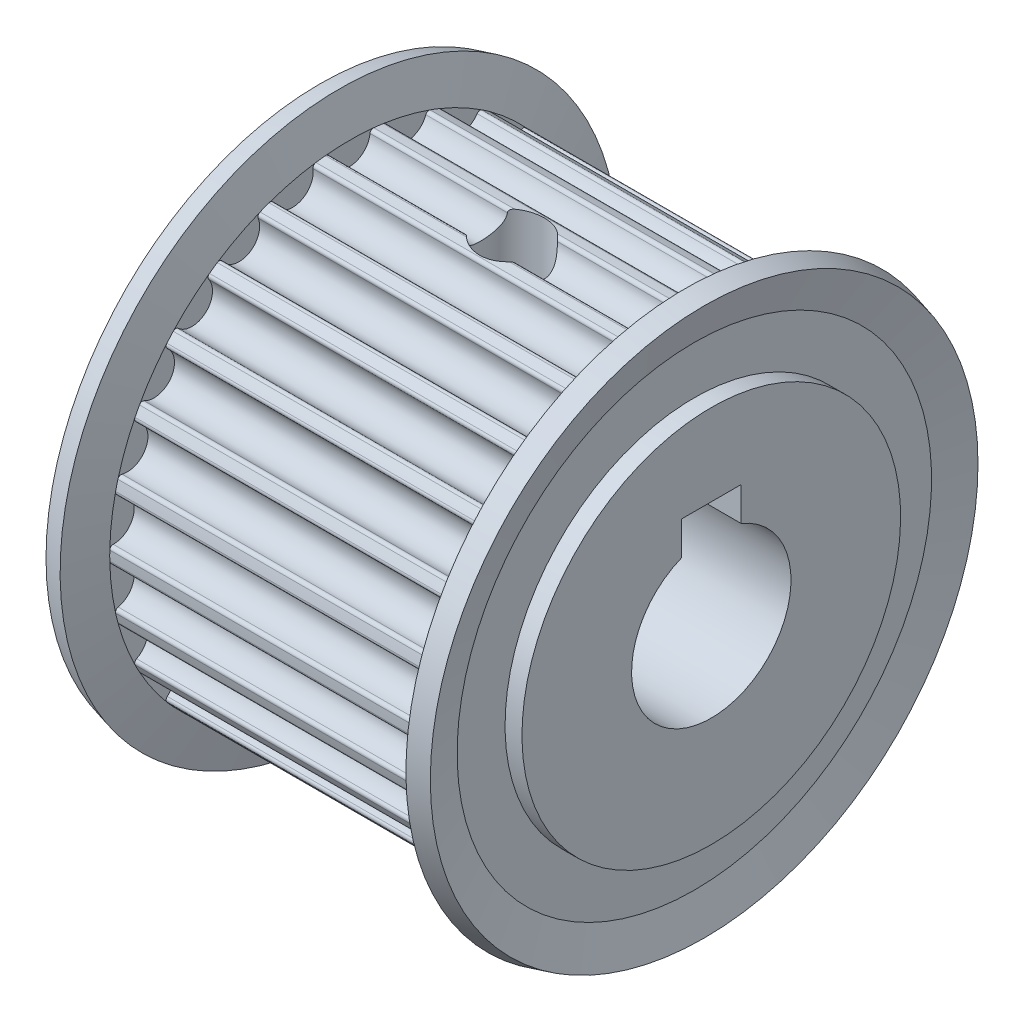
SolidWorks part; units mm, degrees
ref_plane "Front Plane" through (0, 0, 0) normal (0, 0, 1) x (1, 0, 0)
ref_plane "Top Plane" through (0, 0, 0) normal (0, 1, 0) x (1, 0, 0)
ref_plane "Right Plane" through (0, 0, 0) normal (1, 0, 0) x (0, 0, -1)
ref_plane "Plane1" through (0, 0, 0) normal (0, 0, 1) x (1, 0, 0)
sketch "Sketch1" plane through (0, 0, 0) normal (0, 0, 1) x (1, 0, 0)
  line L0 (0, 0) -> (0, 9.5)
  line L1 (0, 9.5) -> (0.85, 9.5)
  line L2 (0.85, 9.5) -> (0.85, 11.9033)
  line L3 (0.85, 11.9033) -> (0.3576, 13.7412)
  line L4 (0.3576, 13.7412) -> (1.3235, 14)
  line L5 (1.3235, 14) -> (1.85, 12.035)
  line L6 (1.85, 12.035) -> (18.15, 12.035)
  line L7 (18.15, 12.035) -> (18.6765, 14)
  line L8 (18.6765, 14) -> (19.6424, 13.7412)
  line L9 (19.6424, 13.7412) -> (19.15, 11.9033)
  line L10 (19.15, 11.9033) -> (19.15, 9.5)
  line L11 (19.15, 9.5) -> (20, 9.5)
  line L12 (20, 9.5) -> (20, 0)
  line L13 (20, 0) -> (0, 0)
  line L14 (20, 0) -> (0, 0) construction
revolve "Revolve1" add sketch "Sketch1" angle 360 about L14 reverse direction yes
ref_plane "Plane2" through (10, 0, 0) normal (1, 0, 0) x (0, 0, -1)
sketch "Sketch2" plane through (10, 0, 0) normal (1, 0, 0) x (0, 0, -1)
  line L0 (-1.2493, 12.352) -> (-1.2111, 11.9739)
  line L1 (1.2111, 11.9739) -> (1.2493, 12.352)
  arc A0 (-1.2111, 11.9739) -> (-1.0248, 11.8218) centre (-1.194, 11.8048) cw
  arc A1 (-1.0248, 11.8218) -> (1.0248, 11.8218) centre (0, 11.925) ccw
  arc A2 (1.0248, 11.8218) -> (1.2111, 11.9739) centre (1.194, 11.8048) cw
  arc A3 (1.2493, 12.352) -> (-1.2493, 12.352) centre (0, 0) ccw
extrude "Cut-Extrude1" cut sketch "Sketch2" against normal blind 8.15 and the other way blind 8.15
ref_plane "Plane3" through (10, 0, 0) normal (1, 0, 0) x (0, 0, -1)
sketch "Sketch3" plane through (10, 0, 0) normal (1, 0, 0) x (0, 0, -1)
  line L0 (-4.169, 11.6941) -> (-4.0414, 11.3361)
  line L1 (-1.6897, 11.9158) -> (-1.743, 12.292)
  arc A0 (-4.0414, 11.3361) -> (-3.8242, 11.233) centre (-3.9843, 11.176) cw
  arc A1 (-3.8242, 11.233) -> (-1.8341, 11.7235) centre (-2.8538, 11.5785) ccw
  arc A2 (-1.8341, 11.7235) -> (-1.6897, 11.9158) centre (-1.6658, 11.7475) cw
  arc A3 (-1.743, 12.292) -> (-4.169, 11.6941) centre (0, 0) ccw
extrude "Cut-Extrude2" cut sketch "Sketch3" against normal blind 8.15 and the other way blind 8.15
ref_plane "Plane4" through (10, 0, 0) normal (1, 0, 0) x (0, 0, -1)
sketch "Sketch4" plane through (10, 0, 0) normal (1, 0, 0) x (0, 0, -1)
  line L0 (-6.8465, 10.3566) -> (-6.6369, 10.0396)
  line L1 (-4.4922, 11.1652) -> (-4.634, 11.5177)
  arc A0 (-6.6369, 10.0396) -> (-6.4013, 9.9914) centre (-6.5432, 9.8977) cw
  arc A1 (-6.4013, 9.9914) -> (-4.5864, 10.9439) centre (-5.5418, 10.5591) ccw
  arc A2 (-4.5864, 10.9439) -> (-4.4922, 11.1652) centre (-4.4288, 11.0075) cw
  arc A3 (-4.634, 11.5177) -> (-6.8465, 10.3566) centre (0, 0) ccw
extrude "Cut-Extrude3" cut sketch "Sketch4" against normal blind 8.15 and the other way blind 8.15
ref_plane "Plane5" through (10, 0, 0) normal (1, 0, 0) x (0, 0, -1)
sketch "Sketch5" plane through (10, 0, 0) normal (1, 0, 0) x (0, 0, -1)
  line L0 (-9.126, 8.4171) -> (-8.8467, 8.1595)
  line L1 (-7.0337, 9.7657) -> (-7.2558, 10.074)
  arc A0 (-8.8467, 8.1595) -> (-8.6064, 8.1692) centre (-8.7217, 8.0443) cw
  arc A1 (-8.6064, 8.1692) -> (-7.0722, 9.5283) centre (-7.9077, 8.926) ccw
  arc A2 (-7.0722, 9.5283) -> (-7.0337, 9.7657) centre (-6.9343, 9.6277) cw
  arc A3 (-7.2558, 10.074) -> (-9.126, 8.4171) centre (0, 0) ccw
extrude "Cut-Extrude4" cut sketch "Sketch5" against normal blind 8.15 and the other way blind 8.15
ref_plane "Plane6" through (10, 0, 0) normal (1, 0, 0) x (0, 0, -1)
sketch "Sketch6" plane through (10, 0, 0) normal (1, 0, 0) x (0, 0, -1)
  line L0 (-10.8752, 5.9886) -> (-10.5423, 5.8053)
  line L1 (-9.1664, 7.7986) -> (-9.4558, 8.0449)
  arc A0 (-10.5423, 5.8053) -> (-10.3113, 5.8721) centre (-10.3934, 5.7233) cw
  arc A1 (-10.3113, 5.8721) -> (-9.147, 7.559) centre (-9.8141, 6.7742) ccw
  arc A2 (-9.147, 7.559) -> (-9.1664, 7.7986) centre (-9.0369, 7.6885) cw
  arc A3 (-9.4558, 8.0449) -> (-10.8752, 5.9886) centre (0, 0) ccw
extrude "Cut-Extrude5" cut sketch "Sketch6" against normal blind 8.15 and the other way blind 8.15
ref_plane "Plane7" through (10, 0, 0) normal (1, 0, 0) x (0, 0, -1)
sketch "Sketch7" plane through (10, 0, 0) normal (1, 0, 0) x (0, 0, -1)
  line L0 (-11.9923, 3.2119) -> (-11.6253, 3.1136)
  line L1 (-10.7663, 5.3784) -> (-11.1063, 5.5482)
  arc A0 (-11.6253, 3.1136) -> (-11.417, 3.2338) centre (-11.461, 3.0697) cw
  arc A1 (-11.417, 3.2338) -> (-10.6902, 5.1503) centre (-11.1501, 4.2287) ccw
  arc A2 (-10.6902, 5.1503) -> (-10.7663, 5.3784) centre (-10.6143, 5.3024) cw
  arc A3 (-11.1063, 5.5482) -> (-11.9923, 3.2119) centre (0, 0) ccw
extrude "Cut-Extrude6" cut sketch "Sketch7" against normal blind 8.15 and the other way blind 8.15
ref_plane "Plane8" through (10, 0, 0) normal (1, 0, 0) x (0, 0, -1)
sketch "Sketch8" plane through (10, 0, 0) normal (1, 0, 0) x (0, 0, -1)
  line L0 (-12.4125, 0.2487) -> (-12.0326, 0.2411)
  line L1 (-11.7406, 2.6455) -> (-12.1113, 2.7291)
  arc A0 (-12.0326, 0.2411) -> (-11.8591, 0.4076) centre (-11.8626, 0.2377) cw
  arc A1 (-11.8591, 0.4076) -> (-11.6121, 2.4423) centre (-11.8381, 1.4374) ccw
  arc A2 (-11.6121, 2.4423) -> (-11.7406, 2.6455) centre (-11.5748, 2.6082) cw
  arc A3 (-12.1113, 2.7291) -> (-12.4125, 0.2487) centre (0, 0) ccw
extrude "Cut-Extrude7" cut sketch "Sketch8" against normal blind 8.15 and the other way blind 8.15
ref_plane "Plane9" through (10, 0, 0) normal (1, 0, 0) x (0, 0, -1)
sketch "Sketch9" plane through (10, 0, 0) normal (1, 0, 0) x (0, 0, -1)
  line L0 (-12.1113, -2.7291) -> (-11.7406, -2.6455)
  line L1 (-12.0326, -0.2411) -> (-12.4125, -0.2487)
  arc A0 (-11.7406, -2.6455) -> (-11.6121, -2.4423) centre (-11.5748, -2.6082) cw
  arc A1 (-11.6121, -2.4423) -> (-11.8591, -0.4076) centre (-11.8381, -1.4374) ccw
  arc A2 (-11.8591, -0.4076) -> (-12.0326, -0.2411) centre (-11.8626, -0.2377) cw
  arc A3 (-12.4125, -0.2487) -> (-12.1113, -2.7291) centre (0, 0) ccw
extrude "Cut-Extrude8" cut sketch "Sketch9" against normal blind 8.15 and the other way blind 8.15
ref_plane "Plane10" through (10, 0, 0) normal (1, 0, 0) x (0, 0, -1)
sketch "Sketch10" plane through (10, 0, 0) normal (1, 0, 0) x (0, 0, -1)
  line L0 (-11.1063, -5.5482) -> (-10.7663, -5.3784)
  line L1 (-11.6253, -3.1136) -> (-11.9923, -3.2119)
  arc A0 (-10.7663, -5.3784) -> (-10.6902, -5.1503) centre (-10.6143, -5.3024) cw
  arc A1 (-10.6902, -5.1503) -> (-11.417, -3.2338) centre (-11.1501, -4.2287) ccw
  arc A2 (-11.417, -3.2338) -> (-11.6253, -3.1136) centre (-11.461, -3.0697) cw
  arc A3 (-11.9923, -3.2119) -> (-11.1063, -5.5482) centre (0, 0) ccw
extrude "Cut-Extrude9" cut sketch "Sketch10" against normal blind 8.15 and the other way blind 8.15
ref_plane "Plane11" through (10, 0, 0) normal (1, 0, 0) x (0, 0, -1)
sketch "Sketch11" plane through (10, 0, 0) normal (1, 0, 0) x (0, 0, -1)
  line L0 (-9.4558, -8.0449) -> (-9.1664, -7.7986)
  line L1 (-10.5423, -5.8053) -> (-10.8752, -5.9886)
  arc A0 (-9.1664, -7.7986) -> (-9.147, -7.559) centre (-9.0369, -7.6885) cw
  arc A1 (-9.147, -7.559) -> (-10.3113, -5.8721) centre (-9.8141, -6.7742) ccw
  arc A2 (-10.3113, -5.8721) -> (-10.5423, -5.8053) centre (-10.3934, -5.7233) cw
  arc A3 (-10.8752, -5.9886) -> (-9.4558, -8.0449) centre (0, 0) ccw
extrude "Cut-Extrude10" cut sketch "Sketch11" against normal blind 8.15 and the other way blind 8.15
ref_plane "Plane12" through (10, 0, 0) normal (1, 0, 0) x (0, 0, -1)
sketch "Sketch12" plane through (10, 0, 0) normal (1, 0, 0) x (0, 0, -1)
  line L0 (-7.2558, -10.074) -> (-7.0337, -9.7657)
  line L1 (-8.8467, -8.1595) -> (-9.126, -8.4171)
  arc A0 (-7.0337, -9.7657) -> (-7.0722, -9.5283) centre (-6.9343, -9.6277) cw
  arc A1 (-7.0722, -9.5283) -> (-8.6064, -8.1692) centre (-7.9077, -8.926) ccw
  arc A2 (-8.6064, -8.1692) -> (-8.8467, -8.1595) centre (-8.7217, -8.0443) cw
  arc A3 (-9.126, -8.4171) -> (-7.2558, -10.074) centre (0, 0) ccw
extrude "Cut-Extrude11" cut sketch "Sketch12" against normal blind 8.15 and the other way blind 8.15
ref_plane "Plane13" through (10, 0, 0) normal (1, 0, 0) x (0, 0, -1)
sketch "Sketch13" plane through (10, 0, 0) normal (1, 0, 0) x (0, 0, -1)
  line L0 (-4.634, -11.5177) -> (-4.4922, -11.1652)
  line L1 (-6.6369, -10.0396) -> (-6.8465, -10.3566)
  arc A0 (-4.4922, -11.1652) -> (-4.5864, -10.9439) centre (-4.4288, -11.0075) cw
  arc A1 (-4.5864, -10.9439) -> (-6.4013, -9.9914) centre (-5.5418, -10.5591) ccw
  arc A2 (-6.4013, -9.9914) -> (-6.6369, -10.0396) centre (-6.5432, -9.8977) cw
  arc A3 (-6.8465, -10.3566) -> (-4.634, -11.5177) centre (0, 0) ccw
extrude "Cut-Extrude12" cut sketch "Sketch13" against normal blind 8.15 and the other way blind 8.15
ref_plane "Plane14" through (10, 0, 0) normal (1, 0, 0) x (0, 0, -1)
sketch "Sketch14" plane through (10, 0, 0) normal (1, 0, 0) x (0, 0, -1)
  line L0 (-1.743, -12.292) -> (-1.6897, -11.9158)
  line L1 (-4.0414, -11.3361) -> (-4.169, -11.6941)
  arc A0 (-1.6897, -11.9158) -> (-1.8341, -11.7235) centre (-1.6658, -11.7475) cw
  arc A1 (-1.8341, -11.7235) -> (-3.8242, -11.233) centre (-2.8538, -11.5785) ccw
  arc A2 (-3.8242, -11.233) -> (-4.0414, -11.3361) centre (-3.9843, -11.176) cw
  arc A3 (-4.169, -11.6941) -> (-1.743, -12.292) centre (0, 0) ccw
extrude "Cut-Extrude13" cut sketch "Sketch14" against normal blind 8.15 and the other way blind 8.15
ref_plane "Plane15" through (10, 0, 0) normal (1, 0, 0) x (0, 0, -1)
sketch "Sketch15" plane through (10, 0, 0) normal (1, 0, 0) x (0, 0, -1)
  line L0 (1.2493, -12.352) -> (1.2111, -11.9739)
  line L1 (-1.2111, -11.9739) -> (-1.2493, -12.352)
  arc A0 (1.2111, -11.9739) -> (1.0248, -11.8218) centre (1.194, -11.8048) cw
  arc A1 (1.0248, -11.8218) -> (-1.0248, -11.8218) centre (0, -11.925) ccw
  arc A2 (-1.0248, -11.8218) -> (-1.2111, -11.9739) centre (-1.194, -11.8048) cw
  arc A3 (-1.2493, -12.352) -> (1.2493, -12.352) centre (0, 0) ccw
extrude "Cut-Extrude14" cut sketch "Sketch15" against normal blind 8.15 and the other way blind 8.15
ref_plane "Plane16" through (10, 0, 0) normal (1, 0, 0) x (0, 0, -1)
sketch "Sketch16" plane through (10, 0, 0) normal (1, 0, 0) x (0, 0, -1)
  line L0 (4.169, -11.6941) -> (4.0414, -11.3361)
  line L1 (1.6897, -11.9158) -> (1.743, -12.292)
  arc A0 (4.0414, -11.3361) -> (3.8242, -11.233) centre (3.9843, -11.176) cw
  arc A1 (3.8242, -11.233) -> (1.8341, -11.7235) centre (2.8538, -11.5785) ccw
  arc A2 (1.8341, -11.7235) -> (1.6897, -11.9158) centre (1.6658, -11.7475) cw
  arc A3 (1.743, -12.292) -> (4.169, -11.6941) centre (0, 0) ccw
extrude "Cut-Extrude15" cut sketch "Sketch16" against normal blind 8.15 and the other way blind 8.15
ref_plane "Plane17" through (10, 0, 0) normal (1, 0, 0) x (0, 0, -1)
sketch "Sketch17" plane through (10, 0, 0) normal (1, 0, 0) x (0, 0, -1)
  line L0 (6.8465, -10.3566) -> (6.6369, -10.0396)
  line L1 (4.4922, -11.1652) -> (4.634, -11.5177)
  arc A0 (6.6369, -10.0396) -> (6.4013, -9.9914) centre (6.5432, -9.8977) cw
  arc A1 (6.4013, -9.9914) -> (4.5864, -10.9439) centre (5.5418, -10.5591) ccw
  arc A2 (4.5864, -10.9439) -> (4.4922, -11.1652) centre (4.4288, -11.0075) cw
  arc A3 (4.634, -11.5177) -> (6.8465, -10.3566) centre (0, 0) ccw
extrude "Cut-Extrude16" cut sketch "Sketch17" against normal blind 8.15 and the other way blind 8.15
ref_plane "Plane18" through (10, 0, 0) normal (1, 0, 0) x (0, 0, -1)
sketch "Sketch18" plane through (10, 0, 0) normal (1, 0, 0) x (0, 0, -1)
  line L0 (9.126, -8.4171) -> (8.8467, -8.1595)
  line L1 (7.0337, -9.7657) -> (7.2558, -10.074)
  arc A0 (8.8467, -8.1595) -> (8.6064, -8.1692) centre (8.7217, -8.0443) cw
  arc A1 (8.6064, -8.1692) -> (7.0722, -9.5283) centre (7.9077, -8.926) ccw
  arc A2 (7.0722, -9.5283) -> (7.0337, -9.7657) centre (6.9343, -9.6277) cw
  arc A3 (7.2558, -10.074) -> (9.126, -8.4171) centre (0, 0) ccw
extrude "Cut-Extrude17" cut sketch "Sketch18" against normal blind 8.15 and the other way blind 8.15
ref_plane "Plane19" through (10, 0, 0) normal (1, 0, 0) x (0, 0, -1)
sketch "Sketch19" plane through (10, 0, 0) normal (1, 0, 0) x (0, 0, -1)
  line L0 (10.8752, -5.9886) -> (10.5423, -5.8053)
  line L1 (9.1664, -7.7986) -> (9.4558, -8.0449)
  arc A0 (10.5423, -5.8053) -> (10.3113, -5.8721) centre (10.3934, -5.7233) cw
  arc A1 (10.3113, -5.8721) -> (9.147, -7.559) centre (9.8141, -6.7742) ccw
  arc A2 (9.147, -7.559) -> (9.1664, -7.7986) centre (9.0369, -7.6885) cw
  arc A3 (9.4558, -8.0449) -> (10.8752, -5.9886) centre (0, 0) ccw
extrude "Cut-Extrude18" cut sketch "Sketch19" against normal blind 8.15 and the other way blind 8.15
ref_plane "Plane20" through (10, 0, 0) normal (1, 0, 0) x (0, 0, -1)
sketch "Sketch20" plane through (10, 0, 0) normal (1, 0, 0) x (0, 0, -1)
  line L0 (11.9923, -3.2119) -> (11.6253, -3.1136)
  line L1 (10.7663, -5.3784) -> (11.1063, -5.5482)
  arc A0 (11.6253, -3.1136) -> (11.417, -3.2338) centre (11.461, -3.0697) cw
  arc A1 (11.417, -3.2338) -> (10.6902, -5.1503) centre (11.1501, -4.2287) ccw
  arc A2 (10.6902, -5.1503) -> (10.7663, -5.3784) centre (10.6143, -5.3024) cw
  arc A3 (11.1063, -5.5482) -> (11.9923, -3.2119) centre (0, 0) ccw
extrude "Cut-Extrude19" cut sketch "Sketch20" against normal blind 8.15 and the other way blind 8.15
ref_plane "Plane21" through (10, 0, 0) normal (1, 0, 0) x (0, 0, -1)
sketch "Sketch21" plane through (10, 0, 0) normal (1, 0, 0) x (0, 0, -1)
  line L0 (12.4125, -0.2487) -> (12.0326, -0.2411)
  line L1 (11.7406, -2.6455) -> (12.1113, -2.7291)
  arc A0 (12.0326, -0.2411) -> (11.8591, -0.4076) centre (11.8626, -0.2377) cw
  arc A1 (11.8591, -0.4076) -> (11.6121, -2.4423) centre (11.8381, -1.4374) ccw
  arc A2 (11.6121, -2.4423) -> (11.7406, -2.6455) centre (11.5748, -2.6082) cw
  arc A3 (12.1113, -2.7291) -> (12.4125, -0.2487) centre (0, 0) ccw
extrude "Cut-Extrude20" cut sketch "Sketch21" against normal blind 8.15 and the other way blind 8.15
ref_plane "Plane22" through (10, 0, 0) normal (1, 0, 0) x (0, 0, -1)
sketch "Sketch22" plane through (10, 0, 0) normal (1, 0, 0) x (0, 0, -1)
  line L0 (12.1113, 2.7291) -> (11.7406, 2.6455)
  line L1 (12.0326, 0.2411) -> (12.4125, 0.2487)
  arc A0 (11.7406, 2.6455) -> (11.6121, 2.4423) centre (11.5748, 2.6082) cw
  arc A1 (11.6121, 2.4423) -> (11.8591, 0.4076) centre (11.8381, 1.4374) ccw
  arc A2 (11.8591, 0.4076) -> (12.0326, 0.2411) centre (11.8626, 0.2377) cw
  arc A3 (12.4125, 0.2487) -> (12.1113, 2.7291) centre (0, 0) ccw
extrude "Cut-Extrude21" cut sketch "Sketch22" against normal blind 8.15 and the other way blind 8.15
ref_plane "Plane23" through (10, 0, 0) normal (1, 0, 0) x (0, 0, -1)
sketch "Sketch23" plane through (10, 0, 0) normal (1, 0, 0) x (0, 0, -1)
  line L0 (11.1063, 5.5482) -> (10.7663, 5.3784)
  line L1 (11.6253, 3.1136) -> (11.9923, 3.2119)
  arc A0 (10.7663, 5.3784) -> (10.6902, 5.1503) centre (10.6143, 5.3024) cw
  arc A1 (10.6902, 5.1503) -> (11.417, 3.2338) centre (11.1501, 4.2287) ccw
  arc A2 (11.417, 3.2338) -> (11.6253, 3.1136) centre (11.461, 3.0697) cw
  arc A3 (11.9923, 3.2119) -> (11.1063, 5.5482) centre (0, 0) ccw
extrude "Cut-Extrude22" cut sketch "Sketch23" against normal blind 8.15 and the other way blind 8.15
ref_plane "Plane24" through (10, 0, 0) normal (1, 0, 0) x (0, 0, -1)
sketch "Sketch24" plane through (10, 0, 0) normal (1, 0, 0) x (0, 0, -1)
  line L0 (9.4558, 8.0449) -> (9.1664, 7.7986)
  line L1 (10.5423, 5.8053) -> (10.8752, 5.9886)
  arc A0 (9.1664, 7.7986) -> (9.147, 7.559) centre (9.0369, 7.6885) cw
  arc A1 (9.147, 7.559) -> (10.3113, 5.8721) centre (9.8141, 6.7742) ccw
  arc A2 (10.3113, 5.8721) -> (10.5423, 5.8053) centre (10.3934, 5.7233) cw
  arc A3 (10.8752, 5.9886) -> (9.4558, 8.0449) centre (0, 0) ccw
extrude "Cut-Extrude23" cut sketch "Sketch24" against normal blind 8.15 and the other way blind 8.15
ref_plane "Plane25" through (10, 0, 0) normal (1, 0, 0) x (0, 0, -1)
sketch "Sketch25" plane through (10, 0, 0) normal (1, 0, 0) x (0, 0, -1)
  line L0 (7.2558, 10.074) -> (7.0337, 9.7657)
  line L1 (8.8467, 8.1595) -> (9.126, 8.4171)
  arc A0 (7.0337, 9.7657) -> (7.0722, 9.5283) centre (6.9343, 9.6277) cw
  arc A1 (7.0722, 9.5283) -> (8.6064, 8.1692) centre (7.9077, 8.926) ccw
  arc A2 (8.6064, 8.1692) -> (8.8467, 8.1595) centre (8.7217, 8.0443) cw
  arc A3 (9.126, 8.4171) -> (7.2558, 10.074) centre (0, 0) ccw
extrude "Cut-Extrude24" cut sketch "Sketch25" against normal blind 8.15 and the other way blind 8.15
ref_plane "Plane26" through (10, 0, 0) normal (1, 0, 0) x (0, 0, -1)
sketch "Sketch26" plane through (10, 0, 0) normal (1, 0, 0) x (0, 0, -1)
  line L0 (4.634, 11.5177) -> (4.4922, 11.1652)
  line L1 (6.6369, 10.0396) -> (6.8465, 10.3566)
  arc A0 (4.4922, 11.1652) -> (4.5864, 10.9439) centre (4.4288, 11.0075) cw
  arc A1 (4.5864, 10.9439) -> (6.4013, 9.9914) centre (5.5418, 10.5591) ccw
  arc A2 (6.4013, 9.9914) -> (6.6369, 10.0396) centre (6.5432, 9.8977) cw
  arc A3 (6.8465, 10.3566) -> (4.634, 11.5177) centre (0, 0) ccw
extrude "Cut-Extrude25" cut sketch "Sketch26" against normal blind 8.15 and the other way blind 8.15
ref_plane "Plane27" through (10, 0, 0) normal (1, 0, 0) x (0, 0, -1)
sketch "Sketch27" plane through (10, 0, 0) normal (1, 0, 0) x (0, 0, -1)
  line L0 (1.743, 12.292) -> (1.6897, 11.9158)
  line L1 (4.0414, 11.3361) -> (4.169, 11.6941)
  arc A0 (1.6897, 11.9158) -> (1.8341, 11.7235) centre (1.6658, 11.7475) cw
  arc A1 (1.8341, 11.7235) -> (3.8242, 11.233) centre (2.8538, 11.5785) ccw
  arc A2 (3.8242, 11.233) -> (4.0414, 11.3361) centre (3.9843, 11.176) cw
  arc A3 (4.169, 11.6941) -> (1.743, 12.292) centre (0, 0) ccw
extrude "Cut-Extrude26" cut sketch "Sketch27" against normal blind 8.15 and the other way blind 8.15
ref_plane "Plane28" through (0, 0, 0) normal (0, 0, 1) x (1, 0, 0)
sketch "Sketch28" plane through (0, 0, 0) normal (0, 0, 1) x (1, 0, 0)
  line L0 (0, 0) -> (0, 4)
  line L1 (0, 4) -> (20, 4)
  line L2 (20, 4) -> (20, 0)
  line L3 (20, 0) -> (0, 0)
  line L4 (20, 0) -> (0, 0) construction
revolve "Cut-Revolve1" cut sketch "Sketch28" angle 360 about L4 reverse direction yes
ref_plane "Plane29" through (10, 0, 0) normal (1, 0, 0) x (0, 0, -1)
sketch "Sketch29" plane through (10, 0, 0) normal (1, 0, 0) x (0, 0, -1)
  line L0 (0, 12.035) -> (1.621, 12.035)
  line L1 (1.621, 12.035) -> (1.621, 0)
  line L2 (1.621, 0) -> (0, 0)
  line L3 (0, 0) -> (0, 12.035)
  line L4 (0, 0) -> (0, 12.035) construction
revolve "Cut-Revolve2" cut sketch "Sketch29" angle 360 about L4 reverse direction yes
ref_plane "Plane30" through (10, 0, 0) normal (1, 0, 0) x (0, 0, -1)
sketch "Sketch30" plane through (10, 0, 0) normal (1, 0, 0) x (0, 0, -1)
  line L0 (9.9046, -6.8367) -> (8.9838, -8.1707)
  line L1 (8.9838, -8.1707) -> (-0.9208, -1.3341)
  line L2 (-0.9208, -1.3341) -> (0, 0)
  line L3 (0, 0) -> (9.9046, -6.8367)
  line L4 (0, 0) -> (9.9046, -6.8367) construction
revolve "Cut-Revolve3" cut sketch "Sketch30" angle 360 about L4 reverse direction yes
ref_plane "Plane31" through (0, 0, 0) normal (1, 0, 0) x (0, 0, -1)
sketch "Sketch31" plane through (0, 0, 0) normal (1, 0, 0) x (0, 0, -1)
  line L0 (-1.5, 0) -> (1.5, 0)
  line L1 (1.5, 0) -> (1.5, 5.4)
  line L2 (1.5, 5.4) -> (-1.5, 5.4)
  line L3 (-1.5, 5.4) -> (-1.5, 0)
extrude "Cut-Extrude27" cut sketch "Sketch31" along normal blind 20
